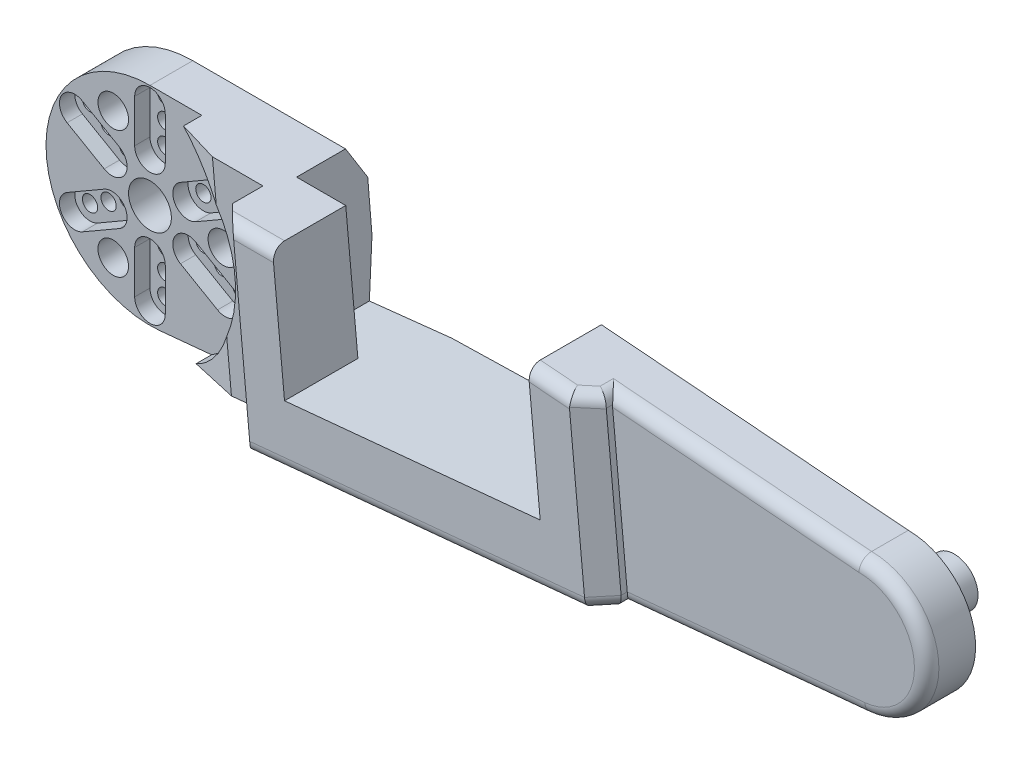
SolidWorks part; units mm, degrees
ref_plane "Front Plane" through (0, 0, 0) normal (0, 0, 1) x (1, 0, 0)
ref_plane "Top Plane" through (0, 0, 0) normal (0, 1, 0) x (1, 0, 0)
ref_plane "Right Plane" through (0, 0, 0) normal (1, 0, 0) x (0, 0, -1)
sketch "Sketch1" plane through (0, 0, 0) normal (0, 0, 1) x (1, 0, 0)
  line L0 (-40.0696, 5.9938) -> (84.9304, 5.9938)
  line L1 (85.984, -15.9556) -> (-38.4413, -27.9281)
  arc A0 (-40.0696, 5.9938) -> (-38.4413, -27.9281) centre (-40.0696, -11.0062) ccw
  arc A1 (84.9304, 5.9938) -> (85.984, -15.9556) centre (84.9304, -5.0062) cw
  circle A2 centre (-40.0696, -11.0062) radius 3.5
  dimension "D5" = 7
  dimension "D1" = 125
  dimension "D2" = 17
  dimension "D3" = 11
extrude "Boss-Extrude1" add sketch "Sketch1" along normal blind 22
sketch "Sketch3" plane through (0, 0, 0) normal (0, 0, -1) x (-1, 0, 0)
  circle A0 centre (40.0696, -11.0062) radius 17
extrude "Cut-Extrude2" cut sketch "Sketch3" against normal blind 2
sketch "Sketch2" plane through (0, 0, 0) normal (0, 0, -1) x (-1, 0, 0)
  line L0 (40.0696, -11.0062) -> (40.0696, 4.1348) construction
  circle A0 centre (40.0696, 3.1938) radius 1.25
  circle A1 centre (40.0696, -0.3062) radius 1.25
  circle A2 centre (40.0696, -3.8062) radius 1.25
  circle A4 centre (40.0696, -11.0062) radius 3.5 construction
  circle A5 centre (52.3671, -3.9062) radius 1.25
  circle A6 centre (49.336, -5.6562) radius 1.25
  circle A7 centre (46.3049, -7.4062) radius 1.25
  circle A8 centre (52.3671, -18.1062) radius 1.25
  circle A9 centre (49.336, -16.3562) radius 1.25
  circle A10 centre (46.3049, -14.6062) radius 1.25
  circle A11 centre (40.0696, -25.2062) radius 1.25
  circle A12 centre (40.0696, -21.7062) radius 1.25
  circle A13 centre (40.0696, -18.2062) radius 1.25
  circle A14 centre (27.772, -18.1062) radius 1.25
  circle A15 centre (30.8031, -16.3562) radius 1.25
  circle A16 centre (33.8342, -14.6062) radius 1.25
  circle A17 centre (27.772, -3.9062) radius 1.25
  circle A18 centre (30.8031, -5.6562) radius 1.25
  circle A19 centre (33.8342, -7.4062) radius 1.25
  point P44 (40.0696, -11.0062)
  dimension "D3" = 2.5
  dimension "D1" = 3.5
  dimension "D2" = 3.5
  dimension "D4" = 7.2
  dimension "D5" = 6
extrude "Cut-Extrude1" cut sketch "Sketch2" against normal up to next
sketch "Sketch4" plane through (0, 0, 22) normal (0, 0, 1) x (1, 0, 0)
  line L0 (-40.0696, 3.1938) -> (-40.0696, -3.8062) construction
  line L1 (-37.9696, 3.1938) -> (-37.9696, -3.8062)
  line L2 (-42.1696, 3.1938) -> (-42.1696, -3.8062)
  line L3 (-27.772, -3.9062) -> (-33.8342, -7.4062) construction
  line L4 (-26.722, -5.7249) -> (-32.7842, -9.2249)
  line L5 (-28.822, -2.0876) -> (-34.8842, -5.5876)
  line L6 (-27.772, -18.1062) -> (-33.8342, -14.6062) construction
  line L7 (-28.822, -19.9249) -> (-34.8842, -16.4249)
  line L8 (-26.722, -16.2876) -> (-32.7842, -12.7876)
  line L9 (-40.0696, -25.2062) -> (-40.0696, -18.2062) construction
  line L10 (-42.1696, -25.2062) -> (-42.1696, -18.2062)
  line L11 (-37.9696, -25.2062) -> (-37.9696, -18.2062)
  line L12 (-52.3671, -18.1062) -> (-46.3049, -14.6062) construction
  line L13 (-53.4171, -16.2876) -> (-47.3549, -12.7876)
  line L14 (-51.3171, -19.9249) -> (-45.2549, -16.4249)
  line L15 (-52.3671, -3.9062) -> (-46.3049, -7.4062) construction
  line L16 (-51.3171, -2.0876) -> (-45.2549, -5.5876)
  line L17 (-53.4171, -5.7249) -> (-47.3549, -9.2249)
  arc A0 (-37.9696, 3.1938) -> (-42.1696, 3.1938) centre (-40.0696, 3.1938) ccw
  arc A1 (-42.1696, -3.8062) -> (-37.9696, -3.8062) centre (-40.0696, -3.8062) ccw
  arc A2 (-26.722, -5.7249) -> (-28.822, -2.0876) centre (-27.772, -3.9062) ccw
  arc A3 (-34.8842, -5.5876) -> (-32.7842, -9.2249) centre (-33.8342, -7.4062) ccw
  arc A4 (-28.822, -19.9249) -> (-26.722, -16.2876) centre (-27.772, -18.1062) ccw
  arc A5 (-32.7842, -12.7876) -> (-34.8842, -16.4249) centre (-33.8342, -14.6062) ccw
  arc A6 (-42.1696, -25.2062) -> (-37.9696, -25.2062) centre (-40.0696, -25.2062) ccw
  arc A7 (-37.9696, -18.2062) -> (-42.1696, -18.2062) centre (-40.0696, -18.2062) ccw
  arc A8 (-53.4171, -16.2876) -> (-51.3171, -19.9249) centre (-52.3671, -18.1062) ccw
  arc A9 (-45.2549, -16.4249) -> (-47.3549, -12.7876) centre (-46.3049, -14.6062) ccw
  arc A10 (-51.3171, -2.0876) -> (-53.4171, -5.7249) centre (-52.3671, -3.9062) ccw
  arc A11 (-47.3549, -9.2249) -> (-45.2549, -5.5876) centre (-46.3049, -7.4062) ccw
  point P4 (-40.0696, -0.3062)
  point P13 (-30.8031, -5.6562)
  point P20 (-30.8031, -16.3562)
  point P27 (-40.0696, -21.7062)
  point P34 (-49.336, -16.3562)
  point P41 (-49.336, -5.6562)
  point P46 (-40.0696, -11.0062)
  dimension "D1" = 4.2
  dimension "D2" = 6
extrude "Cut-Extrude3" cut sketch "Sketch4" against normal blind 3
sketch "Sketch7" plane through (0, 0, 0) normal (0, 0, -1) x (-1, 0, 0)
  line L0 (-84.9304, 5.9938) -> (-69.9304, 5.9938)
  line L1 (-84.9304, 5.9938) -> (40.0696, 5.9938) construction
  line L2 (-69.9304, 5.9938) -> (4.016, -24.6156)
  line L3 (38.4413, -27.9281) -> (-85.984, -15.9556) construction
  line L4 (4.016, -24.6156) -> (-85.984, -15.9556)
  arc A0 (-84.9304, 5.9938) -> (-85.984, -15.9556) centre (-84.9304, -5.0062) ccw construction
  arc A1 (-84.9304, 5.9938) -> (-85.984, -15.9556) centre (-84.9304, -5.0062) ccw
  dimension "D1" = 15
  dimension "D2" = 90
extrude "Cut-Extrude4" cut sketch "Sketch7" against normal blind 10
sketch "Sketch8" plane through (0, 0, 10) normal (0, 0, -1) x (-1, 0, 0)
  circle A0 centre (-84.9304, -5.0062) radius 5.5
  dimension "D1" = 11
extrude "Boss-Extrude4" add sketch "Sketch8" along normal blind 0.5
sketch "Sketch9" plane through (0, 0, 9.5) normal (0, 0, -1) x (-1, 0, 0)
  circle A0 centre (-84.9304, -5.0062) radius 3.9
  dimension "D1" = 7.8
extrude "Boss-Extrude5" add sketch "Sketch9" along normal blind 7
sketch "Sketch11" plane through (0, 0, 0) normal (0, 0, -1) x (-1, 0, 0)
  line L0 (-54.9304, 5.9938) -> (4.016, -24.6156)
  line L1 (4.016, -24.6156) -> (38.4413, -27.9281)
  line L3 (-54.9304, 5.9938) -> (40.0696, 5.9938)
  arc A0 (40.0696, 5.9938) -> (38.4413, -27.9281) centre (40.0696, -11.0062) ccw construction
  arc A1 (40.0696, 5.9938) -> (38.4413, -27.9281) centre (40.0696, -11.0062) ccw
extrude "Boss-Extrude7" add sketch "Sketch11" along normal blind 3
sketch "Sketch12" plane through (0, 5.9938, 0) normal (0, 1, 0) x (1, 0, 0)
  line L0 (54.9304, -4) -> (-40.0696, 3)
  line L1 (-40.0696, 3) -> (54.9304, 3)
  line L4 (54.9304, 0) -> (54.9304, 3)
  line L5 (69.9304, 0) -> (54.9304, 0)
  line L6 (69.9304, 0) -> (69.9304, -4)
  line L7 (69.9304, -4) -> (54.9304, -4)
extrude "Cut-Extrude5" cut sketch "Sketch12" against normal up to next
sketch "Sketch13" plane through (0, 0, 0) normal (1, 0, 0) x (0, 0, -1)
  line L0 (3, 5.9938) -> (-2, -27.9281)
  line L1 (-22, -27.9281) -> (-2, -27.9281) construction
  line L2 (-2, -27.9281) -> (2.88, -27.9281)
  line L3 (0.3434, -24.6156) -> (2.88, -27.9281) construction
  line L4 (2.88, -27.9281) -> (3, 5.9938)
extrude "Cut-Extrude6" cut sketch "Sketch13" against normal up to next and the other way up to next
sketch "Sketch14" plane through (0, 0, 0) normal (1, 0, 0) x (0, 0, -1)
  line L0 (-2, 5.9938) -> (1.998, -0.8041)
  line L1 (1.998, -0.8041) -> (3, 5.9938)
  line L2 (3, 5.9938) -> (-2, 5.9938)
  line L3 (-2, 5.9938) -> (3, 5.9938) construction
extrude "Cut-Extrude7" cut sketch "Sketch14" against normal up to next and the other way up to next
sketch "Sketch15" plane through (0, 0, 22) normal (0, 0, 1) x (1, 0, 0)
  line L0 (-5.0696, -14.6708) -> (36.7373, -10.6481)
  line L1 (36.7373, -10.6481) -> (34.6302, 11.2508)
  line L4 (85.984, -15.9556) -> (-4.016, -24.6156) construction
  line L6 (-5.0696, -14.6708) -> (-7.1767, 7.2281)
  line L8 (-7.1767, 7.2281) -> (34.6302, 11.2508)
  line L9 (-38.4413, -27.9281) -> (85.984, -15.9556) construction
  arc A1 (85.984, -15.9556) -> (84.9304, 5.9938) centre (84.9304, -5.0062) ccw construction
  dimension "D1" = 42
  dimension "D2" = 22
  dimension "D3" = 10
  dimension "D4" = 90
extrude "Cut-Extrude8" cut sketch "Sketch15" against normal up to next
sketch "Sketch21" plane through (0, 0, 22) normal (0, 0, 1) x (1, 0, 0)
  line L3 (35.136, 5.9938) -> (34.749, 10.0165)
  line L4 (34.749, 10.0165) -> (84.9304, 5.9938)
  line L5 (36.7373, -10.6481) -> (35.136, 5.9938) construction
  line L6 (35.136, 5.9938) -> (84.9304, 5.9938)
  line L7 (-7.0579, 5.9938) -> (34.749, 10.0165) construction
  line L8 (-5.0696, -14.6708) -> (36.7373, -10.6481) construction
extrude "Boss-Extrude9" add sketch "Sketch21" against normal up to surface (12 mm away) up to face at (49.7285, -8.302, 10)
sketch "Sketch19" plane through (0, 0, 2) normal (0, 0, -1) x (-1, 0, 0)
  line L1 (-44.7006, -9.8818) -> (-42.6385, 11.549)
  line L2 (-42.6385, 11.549) -> (15.0949, 5.9938)
  line L3 (15.0949, 5.9938) -> (13.0328, -15.437)
  line L4 (13.0328, -15.437) -> (-44.7006, -9.8818)
  line L5 (5.0696, -14.6708) -> (-0.2449, -14.1594) construction
  line L6 (-27.6038, -11.5269) -> (-36.7373, -10.6481) construction
  line L7 (7.0579, 5.9938) -> (40.0696, 5.9938) construction
  dimension "D1" = 58
  dimension "D2" = 8
extrude "Cut-Extrude10" cut sketch "Sketch19" along normal up to next and the other way up to surface other way up to face at (46.4427, -4.6782, 10)
sketch "Sketch20" plane through (0, 0, 10) normal (0, 0, -1) x (-1, 0, 0)
  line L0 (-38.7846, 4.6182) -> (-39.6945, -4.8381) construction
  line L1 (9.9902, -0.075) -> (9.0803, -9.5313) construction
  line L2 (-36.7373, -10.6481) -> (-34.749, 10.0165) construction
  line L3 (13.0328, -15.437) -> (-0.2449, -14.1594) construction
  line L4 (-39.6945, -4.8381) -> (9.0803, -9.5313) construction
  line L5 (-27.6038, -11.5269) -> (-0.2449, -14.1594) construction
  circle A0 centre (9.9902, -0.075) radius 2.5
  circle A1 centre (9.0803, -9.5313) radius 2.5
  circle A2 centre (-39.6945, -4.8381) radius 2.5
  circle A3 centre (-38.7846, 4.6182) radius 2.5
  dimension "D1" = 5
  dimension "D2" = 49
  dimension "D3" = 3.5
  dimension "D4" = 9.5
  dimension "D5" = 9.5
  dimension "D6" = 5.5
extrude "Cut-Extrude11" cut sketch "Sketch20" against normal blind 10
sketch "Sketch27" plane through (0, 0, 10) normal (0, 0, -1) x (-1, 0, 0)
  line L1 (-41.602, -6.538) -> (-73.481, -6.538)
  line L2 (-41.602, -6.538) -> (-41.602, 14.3152)
  line L3 (-41.602, 14.3152) -> (-73.481, 14.3152)
  line L4 (-73.481, -6.538) -> (-73.481, 14.3152)
extrude "Cut-Extrude14" cut sketch "Sketch27" along normal through all
sketch "Sketch28" plane through (2.31, -24.0069, 0) normal (0.0958, -0.9954, 0) x (0.9954, 0.0958, 0)
  line L0 (-39.3113, 22) -> (-57.9395, 22) construction
  line L1 (95.0605, 22) -> (45.0605, 22)
  line L2 (95.0605, 22) -> (95.0605, 18)
  line L3 (95.0605, 18) -> (45.0605, 18)
  line L4 (45.0605, 22) -> (45.0605, 18)
  line L5 (-57.9395, 22) -> (-15.9395, 22)
  line L6 (-57.9395, 22) -> (-57.9395, 14)
  line L7 (-57.9395, 14) -> (-15.9395, 14)
  line L8 (-15.9395, 22) -> (-15.9395, 14)
  line L9 (-57.9395, 22) -> (-57.9395, 2) construction
  dimension "D1" = 50
  dimension "D2" = 42
  dimension "D3" = 8
  dimension "D4" = 4
extrude "Cut-Extrude15" cut sketch "Sketch28" against normal up to next
chamfer "Chamfer1" distance 3 angle 45 2 edges at (45.7712, -5.2233, 22) (-15.0731, -9.7699, 22)
sketch "Sketch29" plane through (0, 0, 14) normal (0, 0, 1) x (1, 0, 0)
  circle A0 centre (-40.0696, -11.0062) radius 19
  dimension "D1" = 38
extrude "Cut-Extrude16" cut sketch "Sketch29" against normal blind 5
sketch "Sketch30" plane through (2.31, -24.0069, 0) normal (0.0958, -0.9954, 0) x (0.9954, 0.0958, 0)
  line L0 (-40.9395, 9) -> (-24.1685, 14)
  line L1 (-32.4542, 14) -> (-15.9395, 14) construction
  line L2 (-24.1685, 14) -> (-40.9395, 14)
  line L3 (-40.9395, 14) -> (-40.9395, 9)
extrude "Cut-Extrude17" cut sketch "Sketch30" against normal through all
fillet "Fillet2" radius 2 10 edges at (45.6702, -19.8347, 20.5) (47.1633, -19.691, 18.5) (44.3791, 9.2445, 18.5) (42.8604, 9.3663, 20.5) (95.9178, -4.4788, 18) (66.5737, -17.8233, 18) (38.0454, 9.7523, 22) (-10.317, 5.9938, 22) (16.8035, -22.6123, 22) (64.6548, 7.6192, 18)
sketch "Sketch31" plane through (0, 0, 9) normal (0, 0, 1) x (1, 0, 0)
  circle A0 centre (-46.0696, -0.6139) radius 2.5
  circle A7 centre (-40.0696, -11.0062) radius 4.7348 construction
  circle A9 centre (-46.3049, -7.4062) radius 1.25 construction
  circle A10 centre (-28.0696, -11.0062) radius 2.5
  circle A11 centre (-46.0696, -21.3985) radius 2.5
  point P15 (-40.0696, -11.0062)
  dimension "D1" = 5
  dimension "D2" = 30
  dimension "D3" = 12
  dimension "D4" = 3
extrude "Cut-Extrude18" cut sketch "Sketch31" against normal up to next
sketch "Sketch32" plane through (0, 0, 9) normal (0, 0, 1) x (1, 0, 0)
  line L0 (-46.3049, -7.4062) -> (-52.3671, -3.9062) construction
  line L1 (-47.5549, -9.5713) -> (-53.6171, -6.0713)
  line L2 (-45.0549, -5.2412) -> (-51.1171, -1.7412)
  line L3 (-40.0696, -3.8062) -> (-40.0696, 3.1938) construction
  line L4 (-42.5696, -3.8062) -> (-42.5696, 3.1938)
  line L5 (-37.5696, -3.8062) -> (-37.5696, 3.1938)
  line L6 (-33.8342, -7.4062) -> (-27.772, -3.9062) construction
  line L7 (-35.0842, -5.2412) -> (-29.022, -1.7412)
  line L8 (-32.5842, -9.5713) -> (-26.522, -6.0713)
  line L9 (-33.8342, -14.6062) -> (-27.772, -18.1062) construction
  line L10 (-32.5842, -12.4412) -> (-26.522, -15.9412)
  line L11 (-35.0842, -16.7713) -> (-29.022, -20.2713)
  line L12 (-40.0696, -18.2062) -> (-40.0696, -25.2062) construction
  line L13 (-37.5696, -18.2062) -> (-37.5696, -25.2062)
  line L14 (-42.5696, -18.2062) -> (-42.5696, -25.2062)
  line L15 (-46.3049, -14.6062) -> (-52.3671, -18.1062) construction
  line L16 (-45.0549, -16.7713) -> (-51.1171, -20.2713)
  line L17 (-47.5549, -12.4412) -> (-53.6171, -15.9412)
  arc A0 (-47.5549, -9.5713) -> (-45.0549, -5.2412) centre (-46.3049, -7.4062) ccw
  arc A1 (-51.1171, -1.7412) -> (-53.6171, -6.0713) centre (-52.3671, -3.9062) ccw
  arc A2 (-42.5696, -3.8062) -> (-37.5696, -3.8062) centre (-40.0696, -3.8062) ccw
  arc A3 (-37.5696, 3.1938) -> (-42.5696, 3.1938) centre (-40.0696, 3.1938) ccw
  arc A4 (-35.0842, -5.2412) -> (-32.5842, -9.5713) centre (-33.8342, -7.4062) ccw
  arc A5 (-26.522, -6.0713) -> (-29.022, -1.7412) centre (-27.772, -3.9062) ccw
  arc A6 (-32.5842, -12.4412) -> (-35.0842, -16.7713) centre (-33.8342, -14.6062) ccw
  arc A7 (-29.022, -20.2713) -> (-26.522, -15.9412) centre (-27.772, -18.1062) ccw
  arc A8 (-37.5696, -18.2062) -> (-42.5696, -18.2062) centre (-40.0696, -18.2062) ccw
  arc A9 (-42.5696, -25.2062) -> (-37.5696, -25.2062) centre (-40.0696, -25.2062) ccw
  arc A10 (-45.0549, -16.7713) -> (-47.5549, -12.4412) centre (-46.3049, -14.6062) ccw
  arc A11 (-53.6171, -15.9412) -> (-51.1171, -20.2713) centre (-52.3671, -18.1062) ccw
  point P4 (-49.336, -5.6562)
  point P14 (-40.0696, -0.3062)
  point P21 (-30.8031, -5.6562)
  point P28 (-30.8031, -16.3562)
  point P35 (-40.0696, -21.7062)
  point P42 (-49.336, -16.3562)
  point P47 (-40.0696, -11.0062)
  dimension "D1" = 2.5
  dimension "D2" = 6
extrude "Cut-Extrude19" cut sketch "Sketch32" against normal blind 2.5
